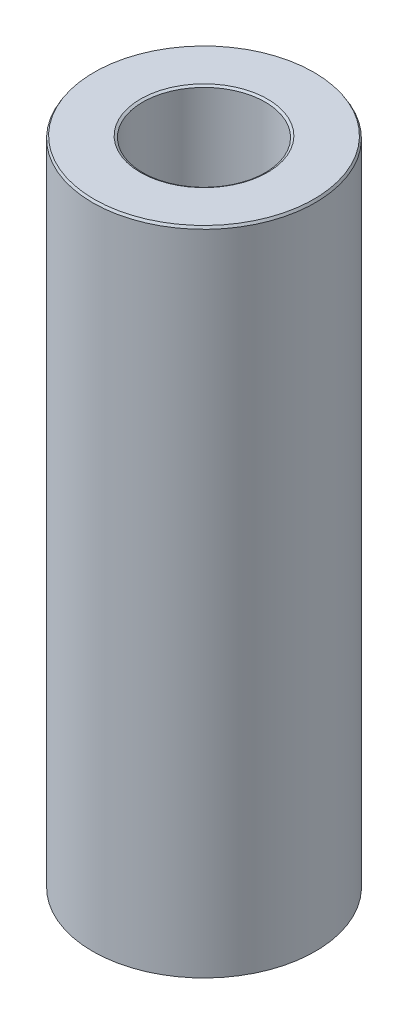
SolidWorks part; units mm, degrees
ref_plane "Front Plane" through (0, 0, 0) normal (0, 0, 1) x (1, 0, 0)
ref_plane "Top Plane" through (0, 0, 0) normal (0, 1, 0) x (1, 0, 0)
ref_plane "Right Plane" through (0, 0, 0) normal (1, 0, 0) x (0, 0, -1)
sketch "Sketch1" plane through (0, 0, 0) normal (0, 1, 0) x (1, 0, 0)
  circle A0 centre (0, 0) radius 30
  dimension "SLEEVE_OD" = 60
extrude "Boss-Extrude1" add sketch "Sketch1" along normal blind 175.6949
sketch "Sketch2" plane through (0, 0, 0) normal (0, 1, 0) x (1, 0, 0)
  circle A0 centre (0, 0) radius 16.4984
  dimension "BORE_D" = 32.9968
extrude "Cut-Extrude1" cut sketch "Sketch2" along normal through all
chamfer "Chamfer1" distance 0.6314 angle 31.312 4 edges at (0, 175.6949, 16.4984) (0, 0, 16.4984) (0, 0, 30) (0, 175.6949, 30) first distance on face at (0, 175.6949, 16.4984) first distance on face at (0, 0, 16.4984) first distance on face at (0, 175.6949, 30)
